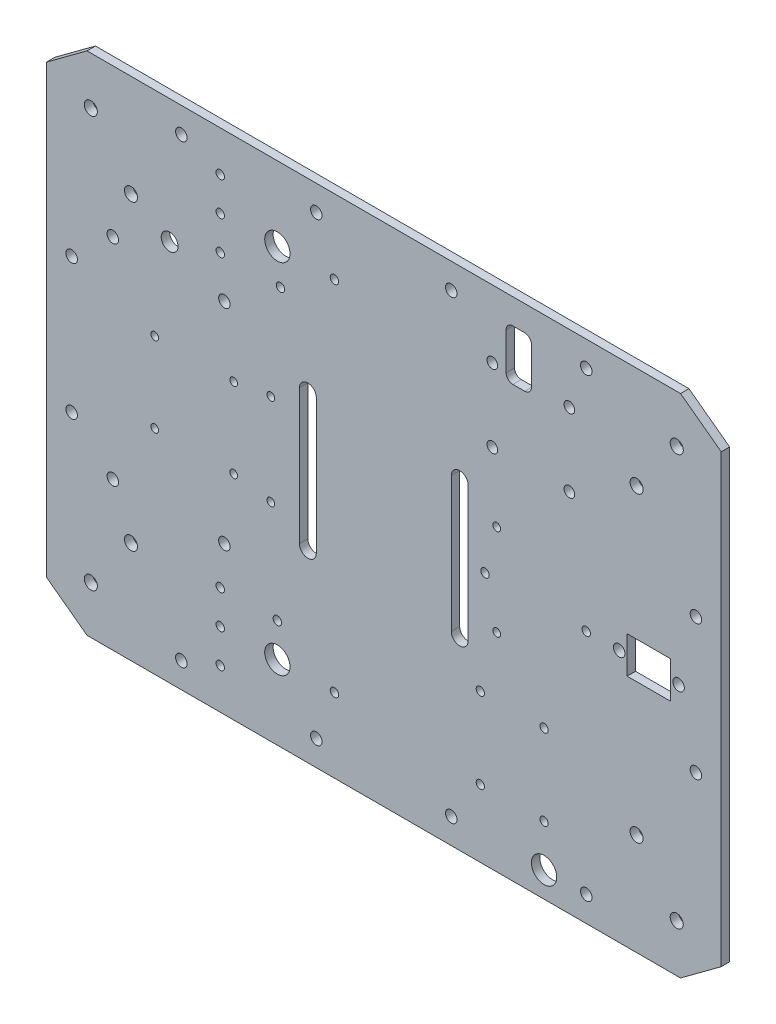
SolidWorks part; units mm, degrees
material "Thornel Mat VMA"
ref_plane "Front Plane" through (0, 0, 0) normal (0, 0, 1) x (1, 0, 0)
ref_plane "Top Plane" through (0, 0, 0) normal (0, 1, 0) x (1, 0, 0)
ref_plane "Right Plane" through (0, 0, 0) normal (1, 0, 0) x (0, 0, -1)
sketch "Sketch1" plane through (0, 0, 0) normal (0, 0, 1) x (1, 0, 0)
  line L0 (-127, 0) -> (127, 0) construction
  line L1 (0, -95.25) -> (0, 95.25) construction
  line L2 (-107.95, 0) -> (-107.95, 41.011) construction
  line L3 (-107.95, 41.011) -> (-95.25, 41.011) construction
  line L4 (-95.25, 41.011) -> (-79.9365, 52.3423) construction
  line L5 (-79.9365, 52.3423) -> (-79.9365, 76.2) construction
  line L6 (-79.9365, 76.2) -> (0, 76.2) construction
  line L7 (-95.25, 41.011) -> (-127, 83.9186) construction
  line L8 (-79.9365, 52.3423) -> (-111.6865, 95.25) construction
  line L9 (-111.6865, -95.25) -> (-127, -83.9186)
  line L10 (111.6865, -95.25) -> (127, -83.9186)
  line L11 (111.6865, 95.25) -> (127, 83.9186)
  line L12 (-87.5933, 46.6767) -> (-95.1475, 56.8856) construction
  line L13 (-95.1475, 56.8856) -> (-110.256, 77.3036) construction
  line L24 (127, -83.9186) -> (127, 83.9186)
  line L26 (111.6865, 95.25) -> (-111.6865, 95.25)
  line L27 (-111.6865, 95.25) -> (-127, 83.9186)
  line L28 (-127, 83.9186) -> (-127, -83.9186)
  line L30 (-111.6865, -95.25) -> (111.6865, -95.25)
  circle A0 centre (-95.1475, 56.8856) radius 2.4638
  circle A1 centre (-110.256, 77.3036) radius 2.4638
  circle A2 centre (110.256, 77.3036) radius 2.4638
  circle A3 centre (95.1475, 56.8856) radius 2.4638
  circle A4 centre (-110.256, -77.3036) radius 2.4638
  circle A5 centre (-95.1475, -56.8856) radius 2.4638
  circle A6 centre (110.256, -77.3036) radius 2.4638
  circle A7 centre (95.1475, -56.8856) radius 2.4638
  point P12 (0, 0)
  dimension "D1" = 190.5
  dimension "D2" = 254
  dimension "D3" = 19.05
  dimension "D4" = 19.05
  dimension "D5" = 12.7
  dimension "D6" = 19.05
  dimension "D7" = 143.5
  dimension "D8" = 12.7
  dimension "D9" = 25.4
extrude "Boss-Extrude1" add sketch "Sketch1" along normal blind 3.175
sketch "Sketch2" plane through (0, 0, 3.175) normal (0, 0, 1) x (1, 0, 0)
  line L0 (-127, 0) -> (127, 0) construction
  line L1 (-127, 83.9186) -> (-127, -83.9186) construction
  line L2 (127, -83.9186) -> (127, 83.9186) construction
  line L3 (57.15, 65.0875) -> (57.15, -65.0875) construction
  line L4 (38.1, 65.0875) -> (76.2, 65.0875)
  line L5 (38.1, 65.0875) -> (38.1, -65.0875)
  line L6 (38.1, -65.0875) -> (76.2, -65.0875)
  line L7 (76.2, 65.0875) -> (76.2, -65.0875)
  line L8 (38.1, 65.0875) -> (76.2, -65.0875) construction
  line L9 (38.1, -65.0875) -> (76.2, 65.0875) construction
  line L10 (57.15, 58.7375) -> (47.625, 58.7375) construction
  line L11 (47.625, 58.7375) -> (38.1, 58.7375) construction
  line L12 (99.7726, 0) -> (99.7726, 35.1373) construction
  line L13 (91.5811, -6.9215) -> (107.9641, -6.9215)
  line L14 (91.5811, -6.9215) -> (91.5811, 6.9215)
  line L15 (91.5811, 6.9215) -> (107.9641, 6.9215)
  line L16 (107.9641, -6.9215) -> (107.9641, 6.9215)
  line L17 (91.5811, -6.9215) -> (107.9641, 6.9215) construction
  line L18 (91.5811, 6.9215) -> (107.9641, -6.9215) construction
  circle A0 centre (42.8625, 58.7375) radius 2.159
  circle A1 centre (42.8625, -58.7375) radius 2.159
  circle A2 centre (71.4375, -58.7375) radius 2.159
  circle A3 centre (71.4375, 58.7375) radius 2.159
  circle A4 centre (110.9486, 0) radius 2.159
  circle A5 centre (88.5966, 0) radius 2.159
  point P6 (57.15, 0)
  point P17 (42.8625, 58.7375)
  point P25 (99.7726, 0)
  dimension "D6" = 13.843
  dimension "D8" = 11.176
  dimension "D1" = 38.1
  dimension "D2" = 130.175
  dimension "D3" = 6.35
  dimension "D4" = 9.525
  dimension "D5" = 69.85
  dimension "D7" = 16.383
extrude "Cut-Extrude1" cut sketch "Sketch2" against normal through all contours L13 L16 L15 L14 | A5 | A4 region at (99.7726, 0, 3.175) region at (110.9486, 0, 3.175) region at (88.5966, 0, 3.175)
sketch "Sketch3" plane through (0, 0, 3.175) normal (0, 0, 1) x (1, 0, 0)
  line L0 (0, 95.25) -> (0, -95.25) construction
  line L1 (111.6865, 95.25) -> (-111.6865, 95.25) construction
  line L2 (-111.6865, -95.25) -> (111.6865, -95.25) construction
  line L3 (127, 0) -> (-127, 0) construction
  line L4 (127, -83.9186) -> (127, 83.9186) construction
  line L5 (-127, 83.9186) -> (-127, -83.9186) construction
  line L8 (119.3433, -89.5843) -> (111.789, -79.3753) construction
  line L10 (111.6865, -95.25) -> (127, -83.9186) construction
  line L11 (111.6865, -95.25) -> (127, -83.9186)
  circle A0 centre (111.789, -79.3753) radius 1.9844
  circle A1 centre (96.6805, -58.9574) radius 1.9844
  dimension "D2" = 3.9688
  dimension "D3" = 3.9688
  dimension "D1" = 12.7
  dimension "D4" = 25.4
sketch "Sketch5" plane through (0, 0, 0) normal (0, 0, -1) x (-1, 0, 0)
  line L0 (-127, 0) -> (127, 0) construction
  line L1 (105.9946, 43.5) -> (55.9947, 43.5) construction
  line L2 (105.9946, 43.5) -> (105.9946, -43.5) construction
  line L3 (105.9946, -43.5) -> (55.9947, -43.5) construction
  line L4 (55.9947, 43.5) -> (55.9947, -43.5) construction
  line L5 (89.4966, 18.0341) -> (89.4966, -18.0339)
  line L6 (67.8946, 95.25) -> (67.8946, -95.25) construction
  line L7 (111.6865, -95.25) -> (-111.6865, -95.25) construction
  line L8 (0, 64.0679) -> (0, -49.8393) construction
  line L9 (-42.5, 17.2) -> (42.5, 17.2) construction
  line L10 (-42.5, 17.2) -> (-42.5, -17.2) construction
  line L11 (-42.5, -17.2) -> (42.5, -17.2) construction
  line L12 (42.5, 17.2) -> (42.5, -17.2) construction
  line L13 (-42.5, 17.2) -> (42.5, -17.2) construction
  line L14 (-42.5, -17.2) -> (42.5, 17.2) construction
  line L15 (46.8402, 60.96) -> (31.75, 60.96) construction
  line L16 (61.5446, -67.31) -> (-87.4336, -67.31) construction
  line L17 (-127, -83.9186) -> (-127, 83.9186) construction
  line L18 (40.0554, 67.31) -> (18.5661, 67.31) construction
  line L19 (-28.575, 25.4) -> (-28.575, -25.4) construction
  line L21 (-127, -83.9186) -> (-127, 83.9186) construction
  line L22 (-50.8, 76.2) -> (80.5946, 76.2) construction
  line L23 (80.5946, 76.2) -> (80.5946, 48.58) construction
  line L25 (80.5946, -77.0458) -> (80.5946, 48.58) construction
  line L26 (127, 0) -> (-127, 0) construction
  line L27 (80.9947, 0) -> (80.9947, -8419.0368) construction
  line L28 (-25.4, 25.4) -> (-25.4, -25.4)
  line L29 (-31.75, 25.4) -> (-31.75, -25.4)
  line L30 (28.575, 25.4) -> (28.575, -25.4) construction
  line L31 (25.4, 25.4) -> (25.4, -25.4)
  line L32 (31.75, 25.4) -> (31.75, -25.4)
  line L33 (71.3384, 0) -> (71.3384, 12.3782) construction
  line L34 (53.4794, 18.0341) -> (89.4966, 18.0341)
  line L35 (53.4794, 18.0341) -> (53.4794, -18.0339)
  line L36 (53.4794, -18.0339) -> (89.4966, -18.0339)
  line L37 (-46.0375, 66.675) -> (-55.5625, 66.675)
  line L38 (-46.0375, 66.675) -> (-46.0375, 85.725)
  line L39 (-46.0375, 85.725) -> (-55.5625, 85.725)
  line L40 (-50.8, 76.2) -> (-50.8, 95.25) construction
  line L41 (-55.5625, 66.675) -> (-55.5625, 85.725)
  line L42 (-46.0375, 66.675) -> (-55.5625, 85.725) construction
  line L43 (-46.0375, 85.725) -> (-55.5625, 66.675) construction
  line L47 (-127, -83.9186) -> (-127, 83.9186) construction
  line L48 (-111.6865, 95.25) -> (111.6865, 95.25) construction
  circle A0 centre (61.5446, -54.61) radius 1.5875
  circle A1 centre (61.5446, -67.31) radius 1.5875
  circle A2 centre (80.5946, 48.58) radius 3.175
  circle A3 centre (-60.325, -85.725) radius 4.7625
  circle A4 centre (61.5446, 54.61) radius 1.5875
  circle A5 centre (61.5446, -80.01) radius 1.5875
  circle A7 centre (40.0554, -67.31) radius 4.7625
  circle A8 centre (61.5446, 67.31) radius 1.5875
  circle A9 centre (61.5446, 80.01) radius 1.5875
  circle A10 centre (40.0554, 67.31) radius 4.7625
  circle A12 centre (59.9952, 39.4995) radius 2.159
  circle A13 centre (101.9941, 39.4995) radius 2.159
  circle A14 centre (59.9952, -39.4995) radius 2.159
  circle A15 centre (101.9941, -39.4995) radius 2.159
  circle A16 centre (18.5661, 67.31) radius 1.5875
  circle A17 centre (38.8861, 54.61) radius 1.5875
  circle A18 centre (18.5661, -67.31) radius 1.5875
  circle A19 centre (40.0554, -54.61) radius 1.5875
  arc A20 (-25.4, 25.4) -> (-31.75, 25.4) centre (-28.575, 25.4) ccw
  arc A21 (-31.75, -25.4) -> (-25.4, -25.4) centre (-28.575, -25.4) ccw
  arc A22 (25.4, 25.4) -> (31.75, 25.4) centre (28.575, 25.4) cw
  arc A23 (31.75, -25.4) -> (25.4, -25.4) centre (28.575, -25.4) cw
  circle A24 centre (56.4794, 15.0341) radius 1.4478
  circle A25 centre (56.4794, -15.0341) radius 1.4478
  circle A26 centre (86.1974, -15.0341) radius 1.4478
  circle A27 centre (86.1974, 15.0341) radius 1.4478
  circle A28 centre (-42.5, 17.2) radius 1.4542
  circle A29 centre (-42.5, -17.2) radius 1.4541
  circle A30 centre (42.5, -17.2) radius 1.4541
  circle A31 centre (42.5, 17.2) radius 1.4542
  point P0 (80.9947, 0)
  point P9 (0, 0)
  point P68 (-60.325, -85.725)
  point P77 (-28.575, 0)
  point P84 (28.575, 0)
  point P89 (71.3384, 0)
  dimension "D10" = 6.35
  dimension "D15" = 2.9997
  dimension "D17" = 66.675
  dimension "D22" = 76.2
  dimension "D25" = 4.0005
  dimension "D45" = 2.8956
  dimension "D9" = 9.525
  dimension "D13" = 14.859
  dimension "D14" = 3
  dimension "D20" = 9.525
  dimension "D8" = 9.525
  dimension "D19" = 19.05
  dimension "D16" = 9.525
  dimension "D1" = 87.0001
  dimension "D2" = 49.9999
  dimension "D4" = 34.4
  dimension "D5" = 85
  dimension "D6" = 6.35
  dimension "D7" = 12.7
  dimension "D11" = 5.08
  dimension "D12" = 25.4
  dimension "D24" = 19.05
  dimension "D26" = 4.0005
  dimension "D38" = 50.8
  dimension "D39" = 6.35
  dimension "D40" = 28.575
  dimension "D41" = 36.0172
  dimension "D42" = 36.068
  dimension "D44" = 3
extrude "Cut-Extrude2" cut sketch "Sketch5" against normal through all contours A2 | A14 | A15 | A13 | A12 | L29 A21 L28 A20 | A23 L4 A22 L31 | A23 L32 A22 L4 | A27 | A24 | A25 | A26
sketch "Sketch6" plane through (0, 0, 0) normal (0, 0, -1) x (-1, 0, 0)
  line L0 (0, 0) -> (-135.1326, 0) construction
  line L1 (0, 0) -> (0, -95.25) construction
  line L2 (111.6865, -95.25) -> (-111.6865, -95.25) construction
  line L3 (-76.2, -95.25) -> (-76.2, -85.725) construction
  line L4 (117.475, 0) -> (117.475, -25.4) construction
  line L5 (127, 0) -> (-127, 0) construction
  line L6 (127, 83.9186) -> (127, -83.9186) construction
  circle A0 centre (-76.2, -85.725) radius 2.159
  circle A1 centre (-25.4, -85.725) radius 2.159
  circle A2 centre (25.4, -85.725) radius 2.159
  circle A3 centre (76.2, -85.725) radius 2.159
  circle A4 centre (76.2, 85.725) radius 2.159
  circle A5 centre (25.4, 85.725) radius 2.159
  circle A6 centre (-25.4, 85.725) radius 2.159
  circle A7 centre (-76.2, 85.725) radius 2.159
  circle A8 centre (117.475, -25.4) radius 2.159
  circle A9 centre (117.475, 25.4) radius 2.159
  circle A10 centre (-117.475, 25.4) radius 2.159
  circle A11 centre (-117.475, -25.4) radius 2.159
  dimension "D2" = 9.525
  dimension "D3" = 76.2
  dimension "D5" = 9.525
  dimension "D6" = 25.4
  dimension "D4" = 4
extrude "Cut-Extrude3" cut sketch "Sketch6" against normal through all
extrude "Cut-Extrude4" cut sketch "Sketch5<3>" against normal through all contours A28 | A29 | A31 | A30
sketch "Sketch5<3>" plane through (0, 0, 0) normal (0, 0, -1) x (-1, 0, 0) same geometry as "Sketch5"
extrude "Cut-Extrude5" cut sketch "Sketch5<4>" against normal through all contours A3 | A10 | A9 | A8 | A4 | A0 | A1 | A5 | A7 region at (60.325, -85.725, 0)
sketch "Sketch5<4>" plane through (0, 0, 0) normal (0, 0, -1) x (-1, 0, 0) same geometry as "Sketch5"
extrude "Cut-Extrude6" cut sketch "Sketch5<5>" against normal blind 2.54 contours A18 | A17 | A16
sketch "Sketch5<5>" plane through (0, 0, 0) normal (0, 0, -1) x (-1, 0, 0) same geometry as "Sketch5"
extrude "Cut-Extrude7" cut sketch "Sketch5<6>" against normal through all contours A17 | A18 | A16
sketch "Sketch5<6>" plane through (0, 0, 0) normal (0, 0, -1) x (-1, 0, 0) same geometry as "Sketch5"
extrude "Cut-Extrude8" cut sketch "Sketch5<7>" against normal blind 2.54 and the other way blind 7.62 contours L41 L37 L38 L39 | A19
sketch "Sketch5<7>" plane through (0, 0, 0) normal (0, 0, -1) x (-1, 0, 0) same geometry as "Sketch5"
extrude "Cut-Extrude9" cut sketch "Sketch5<9>" against normal through all contours A19
sketch "Sketch5<9>" plane through (0, 0, 0) normal (0, 0, -1) x (-1, 0, 0) same geometry as "Sketch5"
extrude "Cut-Extrude17" cut sketch "Sketch5<15>" against normal through all both and the other way through all contours L39 L41 L37 L38
sketch "Sketch5<15>" plane through (0, 0, 0) normal (0, 0, -1) x (-1, 0, 0) same geometry as "Sketch5"
fillet "Fillet1" radius 2.54 1 edges at (55.5625, 85.725, 1.5875) type face fillet first side face at (55.5625, 76.2, 1.5875) second side face at (50.8, 85.725, 1.5875)
fillet "Fillet2" radius 2.54 1 edges at (46.0375, 85.725, 1.5875) type face fillet first side face at (49.53, 85.725, 1.5875) second side face at (46.0375, 76.2, 1.5875)
fillet "Fillet3" radius 2.54 1 edges at (46.0375, 66.675, 1.5875) type face fillet first side face at (50.8, 66.675, 1.5875) second side face at (46.0375, 74.93, 1.5875)
fillet "Fillet4" radius 2.54 1 edges at (55.5625, 66.675, 1.5875) type face fillet first side face at (52.07, 66.675, 1.5875) second side face at (55.5625, 74.93, 1.5875)
sketch "Sketch9" plane through (0, 0, 3.175) normal (0, 0, 1) x (1, 0, 0)
  line L0 (127, -83.9186) -> (127, 83.9186) construction
  line L1 (36.325, -39.45) -> (60.325, -39.45) construction
  line L2 (36.325, -39.45) -> (36.325, -69.85) construction
  line L3 (36.325, -69.85) -> (60.325, -69.85) construction
  line L4 (60.325, -39.45) -> (60.325, -69.85) construction
  line L5 (-111.6865, -95.25) -> (111.6865, -95.25) construction
  line L6 (127, -83.9186) -> (127, 83.9186) construction
  line L7 (69.85, 69.85) -> (40.85, 69.85) construction
  line L8 (69.85, 69.85) -> (69.85, 42.35) construction
  line L9 (69.85, 42.35) -> (40.85, 42.35) construction
  line L10 (40.85, 69.85) -> (40.85, 42.35) construction
  line L11 (111.6865, 95.25) -> (-111.6865, 95.25) construction
  line L12 (127, 0) -> (0, 0) construction
  circle A0 centre (36.325, -39.45) radius 1.55
  circle A1 centre (60.325, -39.45) radius 1.55
  circle A2 centre (60.325, -69.85) radius 1.55
  circle A3 centre (36.325, -69.85) radius 1.55
  circle A4 centre (69.85, 69.85) radius 2
  circle A5 centre (40.85, 69.85) radius 2
  circle A6 centre (40.85, 42.35) radius 2
  circle A7 centre (69.85, 42.35) radius 2
  circle A8 centre (76.2, 0) radius 1.5875
  circle A9 centre (38.1, 0) radius 1.5875
  dimension "D1" = 3.1
  dimension "D6" = 4
  dimension "D11" = 3.175
  dimension "D12" = 3.175
  dimension "D13" = 38.1
  dimension "D2" = 30.4
  dimension "D3" = 24
  dimension "D4" = 66.675
  dimension "D5" = 25.4
  dimension "D7" = 29
  dimension "D8" = 27.5
  dimension "D9" = 57.15
  dimension "D10" = 25.4
  dimension "D14" = 50.8
extrude "Cut-Extrude18" cut sketch "Sketch9" against normal through all
